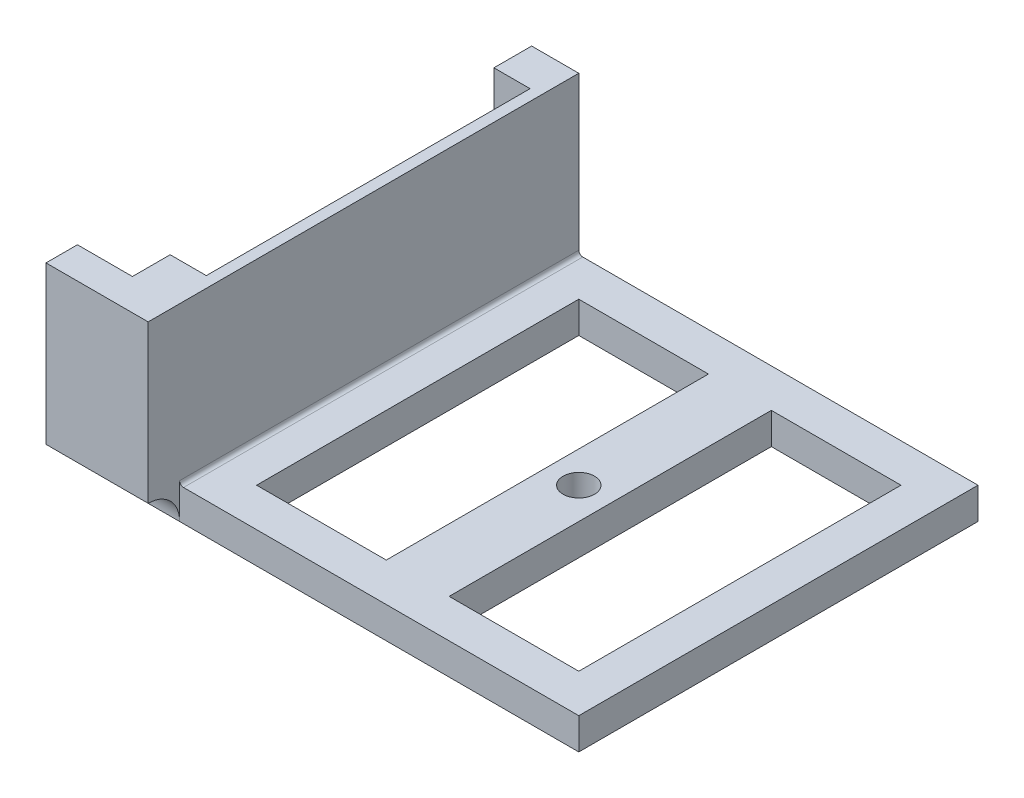
SolidWorks part; units mm, degrees
ref_plane "Front Plane" through (0, 0, 0) normal (0, 0, 1) x (1, 0, 0)
ref_plane "Top Plane" through (0, 0, 0) normal (0, 1, 0) x (1, 0, 0)
ref_plane "Right Plane" through (0, 0, 0) normal (1, 0, 0) x (0, 0, -1)
sketch "Sketch1" plane through (0, 0, 0) normal (0, 1, 0) x (1, 0, 0)
  line L0 (2, 10.25) -> (10.25, 10.25)
  line L1 (12.5, 12.5) -> (-12.5, 12.5) construction
  line L2 (12.5, 12.5) -> (12.5, -12.5) construction
  line L3 (12.5, -12.5) -> (-12.5, -12.5) construction
  line L4 (-12.5, 12.5) -> (-12.5, -12.5) construction
  line L5 (12.7, 12.7) -> (-12.7, 12.7)
  line L6 (-12.7, 12.7) -> (-12.7, -12.7)
  line L7 (12.7, -12.7) -> (-12.7, -12.7)
  line L8 (12.7, 12.7) -> (12.7, -12.7)
  line L9 (-10.25, 10.25) -> (-2, 10.25)
  line L10 (-10, 10) -> (10, 10) construction
  line L11 (-10, 10) -> (-10, -10) construction
  line L12 (-10, -10) -> (10, -10) construction
  line L13 (10, 10) -> (10, -10) construction
  line L14 (10.25, 10.25) -> (10.25, -10.25)
  line L15 (-10.25, -10.25) -> (-2, -10.25)
  line L16 (-10.25, 10.25) -> (-10.25, -10.25)
  line L17 (0, 10.25) -> (0, -10.25) construction
  line L18 (-2, 10.25) -> (-2, -10.25)
  line L19 (2, 10.25) -> (2, -10.25)
  line L20 (-12.7, 12.7) -> (-15.7, 12.7)
  line L21 (-12.7, 12.7) -> (-12.7, -12.7)
  line L22 (-12.7, -12.7) -> (-15.7, -12.7)
  line L23 (-15.7, 12.7) -> (-15.7, -12.7)
  line L24 (2, -10.25) -> (10.25, -10.25)
  circle A0 centre (0, 0) radius 1
  point P21 (0, 0)
sketch "Sketch2" plane through (0, 0, 0) normal (0, 1, 0) x (1, 0, 0)
  line L0 (-12.7, 12.7) -> (-15.7, 12.7) construction
  line L1 (-15.7, 12.7) -> (-15.7, -12.7) construction
  line L2 (-12.7, -12.7) -> (-15.7, -12.7) construction
  line L4 (2, 10.25) -> (10.25, 10.25) construction
  line L5 (10.25, 10.25) -> (10.25, -10.25) construction
  line L6 (2, -10.25) -> (10.25, -10.25) construction
  line L7 (2, 10.25) -> (2, -10.25) construction
  line L8 (-10.25, 10.25) -> (-2, 10.25) construction
  line L9 (-2, 10.25) -> (-2, -10.25) construction
  line L10 (-10.25, -10.25) -> (-2, -10.25) construction
  line L11 (-10.25, 10.25) -> (-10.25, -10.25) construction
  line L12 (12.7, 12.7) -> (-12.7, 12.7) construction
  line L14 (12.7, -12.7) -> (-12.7, -12.7) construction
  line L15 (12.7, 12.7) -> (12.7, -12.7) construction
  line L16 (-12.7, 12.7) -> (-15.7, 12.7)
  line L17 (-15.7, 12.7) -> (-15.7, -12.7)
  line L18 (-12.7, -12.7) -> (-15.7, -12.7)
  line L20 (2, 10.25) -> (10.25, 10.25)
  line L21 (10.25, 10.25) -> (10.25, -10.25)
  line L22 (2, -10.25) -> (10.25, -10.25)
  line L23 (2, 10.25) -> (2, -10.25)
  line L24 (-10.25, 10.25) -> (-2, 10.25)
  line L25 (-2, 10.25) -> (-2, -10.25)
  line L26 (-10.25, -10.25) -> (-2, -10.25)
  line L27 (-10.25, 10.25) -> (-10.25, -10.25)
  line L28 (12.7, 12.7) -> (-12.7, 12.7)
  line L30 (12.7, -12.7) -> (-12.7, -12.7)
  line L31 (12.7, 12.7) -> (12.7, -12.7)
  circle A0 centre (0, 0) radius 1 construction
  circle A1 centre (0, 0) radius 1
extrude "Boss-Extrude1" add sketch "Sketch2" along normal blind 2
sketch "Sketch3" plane through (0, 2, 0) normal (0, 1, 0) x (1, 0, 0)
  line L0 (-15.7, 12.7) -> (-15.7, -12.7) construction
  line L1 (-12.7, 12.7) -> (-15.7, 12.7) construction
  line L2 (-12.7, -12.7) -> (-15.7, -12.7) construction
  line L3 (-12.7, 12.7) -> (-12.7, -12.7) construction
  line L4 (-15.7, 12.7) -> (-15.7, -12.7)
  line L5 (-12.7, 12.7) -> (-15.7, 12.7)
  line L6 (-12.7, -12.7) -> (-15.7, -12.7)
  line L7 (-12.7, 12.7) -> (-12.7, -12.7)
extrude "Boss-Extrude2" add sketch "Sketch3" along normal blind 10
fillet "Fillet1" radius 0.25 1 edges at (-12.7, 2, 0)
sketch "Sketch5" plane through (0, 0, 12.7) normal (0, 0, 1) x (1, 0, 0)
  line L1 (-19.2, 12) -> (-12.7, 12)
  line L2 (-19.2, 12) -> (-19.2, 2)
  line L3 (-19.2, 2) -> (-12.7, 2)
  line L5 (-15.7, 12) -> (-12.7, 12) construction
  line L6 (-12.7, 12) -> (-12.7, 2)
  point P8 (-14.2, 12)
  point P9 (-15.95, 12)
  dimension "D1" = 10
  dimension "D2" = 6.5
extrude "Boss-Extrude3" add sketch "Sketch5" along normal blind 2
sketch "Sketch6" plane through (0, 0, 0) normal (0, -1, 0) x (1, 0, 0)
  line L0 (-15.7, -12.7) -> (-15.7, 12.7) construction
  line L1 (-15.7, 10) -> (-13.7, 10) construction
  line L2 (-15.7, 10) -> (-15.7, -10) construction
  line L3 (-15.7, -10) -> (-13.7, -10) construction
  line L4 (-13.7, 10) -> (-13.7, -10) construction
  line L5 (-16, 10.3) -> (-16, -10.3)
  line L6 (-16, -10.3) -> (-13.4, -10.3)
  line L7 (-13.4, 10.3) -> (-13.4, -10.3)
  line L8 (-16, 10.3) -> (-13.4, 10.3)
  point P6 (-13.7, 0)
  dimension "D1" = 20
  dimension "D2" = 2
  dimension "D3" = 0.3
extrude "Cut-Extrude1" cut sketch "Sketch6" against normal through all both and the other way through all
fillet "Fillet3" radius 2 1 edges at (-14.2, 2, 12.7)
